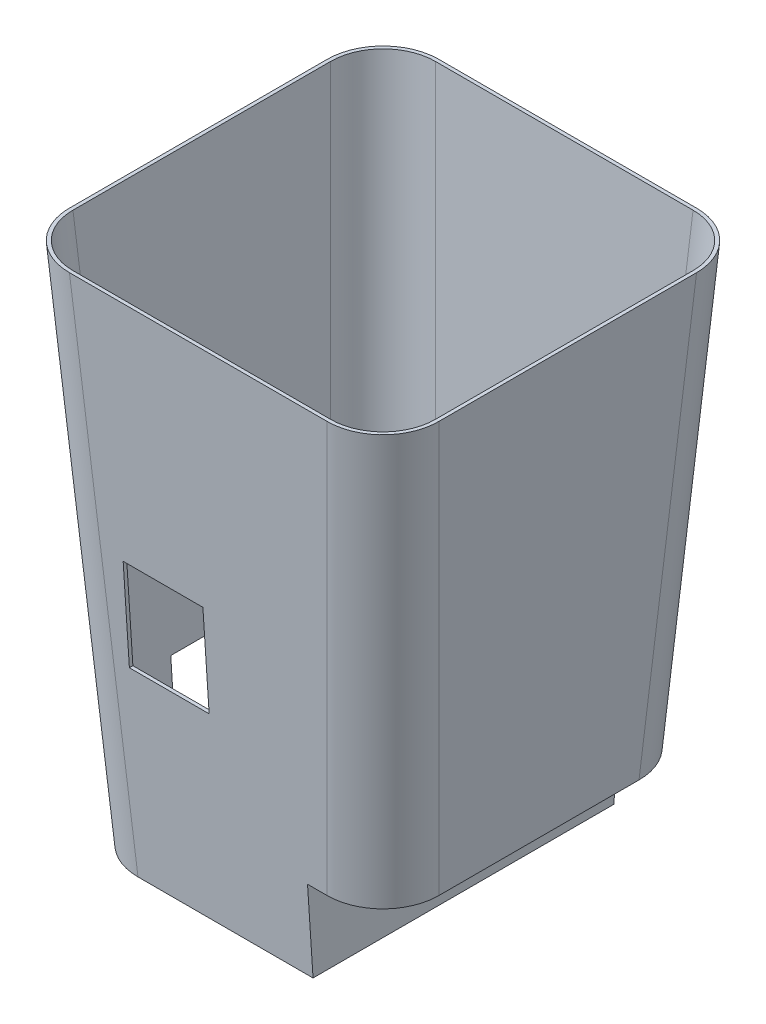
SolidWorks part; units mm, degrees
material "ABS"
ref_plane "Front Plane" through (0, 0, 0) normal (0, 0, 1) x (1, 0, 0)
ref_plane "Top Plane" through (0, 0, 0) normal (0, 1, 0) x (1, 0, 0)
ref_plane "Right Plane" through (0, 0, 0) normal (1, 0, 0) x (0, 0, -1)
sketch "Sketch1" plane through (0, 0, 0) normal (0, 1, 0) x (1, 0, 0)
  line L1 (273.05, 273.05) -> (-273.05, 273.05)
  line L2 (273.05, 273.05) -> (273.05, -273.05)
  line L3 (273.05, -273.05) -> (-273.05, -273.05)
  line L4 (-273.05, 273.05) -> (-273.05, -273.05)
  line L5 (273.05, 273.05) -> (-273.05, -273.05) construction
  line L6 (273.05, -273.05) -> (-273.05, 273.05) construction
  point P0 (0, 0)
  dimension "D1" = 546.1
ref_plane "Plane1" through (0, 949.96, 0) normal (0, 1, 0) x (1, 0, 0)
sketch "Sketch3" plane through (0, 949.96, 0) normal (0, 1, 0) x (1, 0, 0)
  line L1 (335.28, 335.28) -> (-335.28, 335.28)
  line L2 (335.28, 335.28) -> (335.28, -335.28)
  line L3 (335.28, -335.28) -> (-335.28, -335.28)
  line L4 (-335.28, 335.28) -> (-335.28, -335.28)
  line L5 (335.28, 335.28) -> (-335.28, -335.28) construction
  line L6 (335.28, -335.28) -> (-335.28, 335.28) construction
  point P0 (0, 0)
  dimension "D1" = 670.56
loft "Loft1" add profiles "Sketch1", "Sketch3" connector at (273.05, 0, -273.05) connector at (335.28, 949.96, -335.28)
sketch "Sketch4" plane through (0, 0, 0) normal (0, 0, 1) x (1, 0, 0)
  line L1 (303.7403, 0) -> (146.05, 0)
  line L2 (303.7403, 0) -> (303.7403, 152.4)
  line L3 (303.7403, 152.4) -> (146.05, 152.4)
  line L4 (146.05, 0) -> (146.05, 152.4)
  dimension "D1" = 127
  dimension "D2" = 152.4
extrude "Cut-Extrude1" cut sketch "Sketch4" against normal through all both and the other way through all
fillet "Fillet1" radius 101.6 4 edges
shell "Shell1" thickness 6.35 removed face at (0, 949.96, 0)
sketch "Sketch5" plane through (0, 0, 0) normal (0, 0, 1) x (1, 0, 0)
  line L0 (-171.6673, 0) -> (146.05, 0) construction
  line L1 (-164.7952, 516.5725) -> (-20.0152, 516.5725)
  line L2 (-164.7952, 516.5725) -> (-164.7952, 343.535)
  line L3 (-164.7952, 343.535) -> (-20.0152, 343.535)
  line L4 (-20.0152, 516.5725) -> (-20.0152, 343.535)
  line L5 (146.05, 0) -> (146.05, 152.4) construction
  dimension "D1" = 343.535
  dimension "D2" = 166.0652
  dimension "D3" = 173.0375
  dimension "D4" = 144.78
extrude "Cut-Extrude2" cut sketch "Sketch5" along normal blind 431.8
sketch "Sketch6" plane through (0, 0, 0) normal (1, 0, 0) x (0, 0, -1)
  line L0 (0, 0) -> (0, 50000) construction
  line L1 (273.05, 0) -> (-273.05, 0) construction
  line L3 (-104.775, 6.35) -> (104.775, 6.35)
  line L4 (-104.775, 6.35) -> (-104.775, 209.55)
  line L5 (-104.775, 209.55) -> (104.775, 209.55)
  line L6 (104.775, 6.35) -> (104.775, 209.55)
  line L7 (267.1024, 6.35) -> (-267.1024, 6.35) construction
  point P4 (0, 0)
  point P11 (0, 209.55)
  dimension "D1" = 203.2
  dimension "D2" = 209.55
extrude "Cut-Extrude3" cut sketch "Sketch6" against normal blind 679.704
equation "\"D3@Sketch5\"=4+(5.625/2)"
